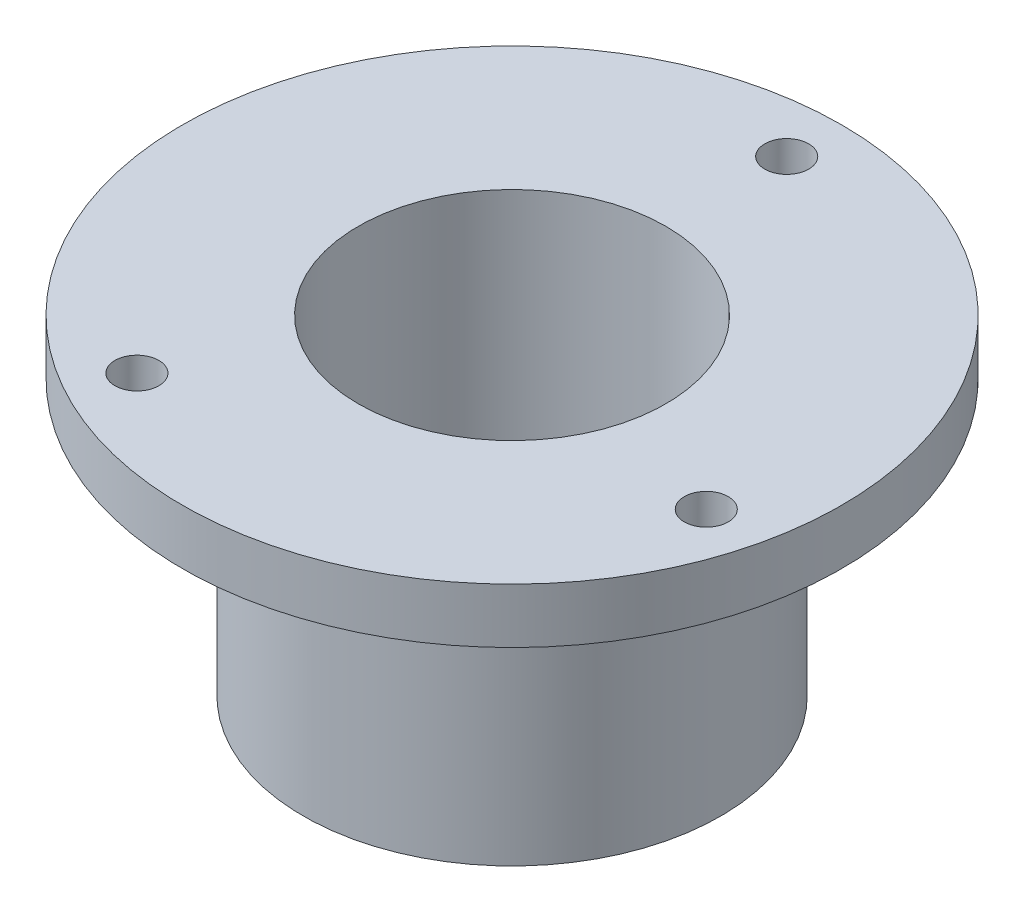
SolidWorks part; units mm, degrees
ref_plane "Front Plane" through (0, 0, 0) normal (0, 0, 1) x (1, 0, 0)
ref_plane "Top Plane" through (0, 0, 0) normal (0, 1, 0) x (1, 0, 0)
ref_plane "Right Plane" through (0, 0, 0) normal (1, 0, 0) x (0, 0, -1)
sketch "Sketch1" plane through (0, 0, 0) normal (0, 0, 1) x (1, 0, 0)
  line L0 (0, 0) -> (0, 15) construction
  line L1 (9.5, 0) -> (9.5, 12.5)
  line L2 (9.5, 12.5) -> (15, 12.5)
  line L3 (15, 12.5) -> (15, 15)
  line L4 (15, 15) -> (7, 15)
  line L5 (7, 15) -> (7, 0)
  line L6 (7, 0) -> (9.5, 0)
  line L7 (0, 0) -> (7, 0) construction
  point P4 (0, 0)
  dimension "D1" = 15
  dimension "D2" = 15
  dimension "D3" = 7
  dimension "D4" = 2.5
revolve "Revolve1" add sketch "Sketch1" angle 360 about L0
sketch "Sketch2" plane through (0, 15, 0) normal (0, 1, 0) x (1, 0, 0)
  line L0 (0, 0) -> (0, 12.5) construction
  line L1 (0, 0) -> (12.0741, -3.2352) construction
  circle A0 centre (0, 0) radius 12.5 construction
  circle A1 centre (0, 12.5) radius 1
  circle A2 centre (0, 0) radius 12.5 construction
  circle A4 centre (0, 0) radius 12.5 construction
  circle A6 centre (10.8253, -6.25) radius 1 [skipped]
  circle A7 centre (-10.8253, -6.25) radius 1 [skipped]
  circle A8 centre (0, 0) radius 12.5 construction
  circle A9 centre (12.0741, -3.2352) radius 1
  circle A10 centre (0, 0) radius 12.5 construction
  circle A11 centre (-6.25, -10.8253) radius 1
  dimension "D1" = 25
  dimension "D2" = 2
  dimension "D5" = 105
  dimension "D3" = 3
  dimension "D4" = 3
extrude "Cut-Extrude1" cut sketch "Sketch2" against normal through all
